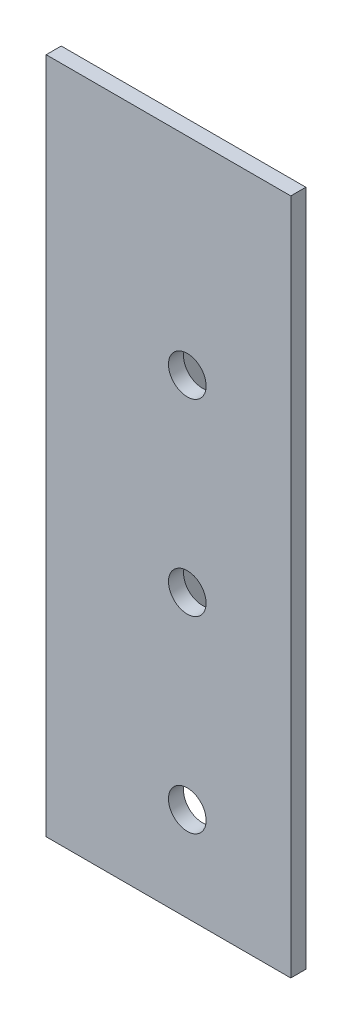
SolidWorks part; units mm, degrees
ref_plane "Спереди" through (0, 0, 0) normal (0, 0, 1) x (1, 0, 0)
ref_plane "Сверху" through (0, 0, 0) normal (0, 1, 0) x (1, 0, 0)
ref_plane "Справа" through (0, 0, 0) normal (1, 0, 0) x (0, 0, -1)
sketch "Эскиз1" plane through (0, 0, 0) normal (0, 1, 0) x (1, 0, 0)
  line L0 (0, 0) -> (65, 0)
  line L1 (0, 0) -> (0, 65)
extrude "Вытянуть-Тонкостенный1" add sketch "Эскиз1" along normal blind 180 thin thin type one direction wall 4
sketch "Эскиз6" plane through (0, 0, 0) normal (0, 0, -1) x (-1, 0, 0)
  circle A0 centre (-37.5, 25) radius 5
  circle A1 centre (-37.5, 75) radius 5
  circle A2 centre (-37.5, 125) radius 5
  dimension "D1" = 3
extrude "Вырез-Вытянуть1" cut sketch "Эскиз6" along normal blind 10
sketch "Эскиз9" plane through (0, 0, 0) normal (-1, 0, 0) x (0, 0, 1)
  line L0 (-4, 180) -> (-65, 180)
  line L1 (0, 180) -> (-65, 180) construction
  line L2 (-65, 119) -> (-65, 180)
  line L3 (-65, 180) -> (-65, 0) construction
  line L4 (-4, 180) -> (-65, 119)
extrude "Вырез-Вытянуть2" cut sketch "Эскиз9" against normal blind 10
